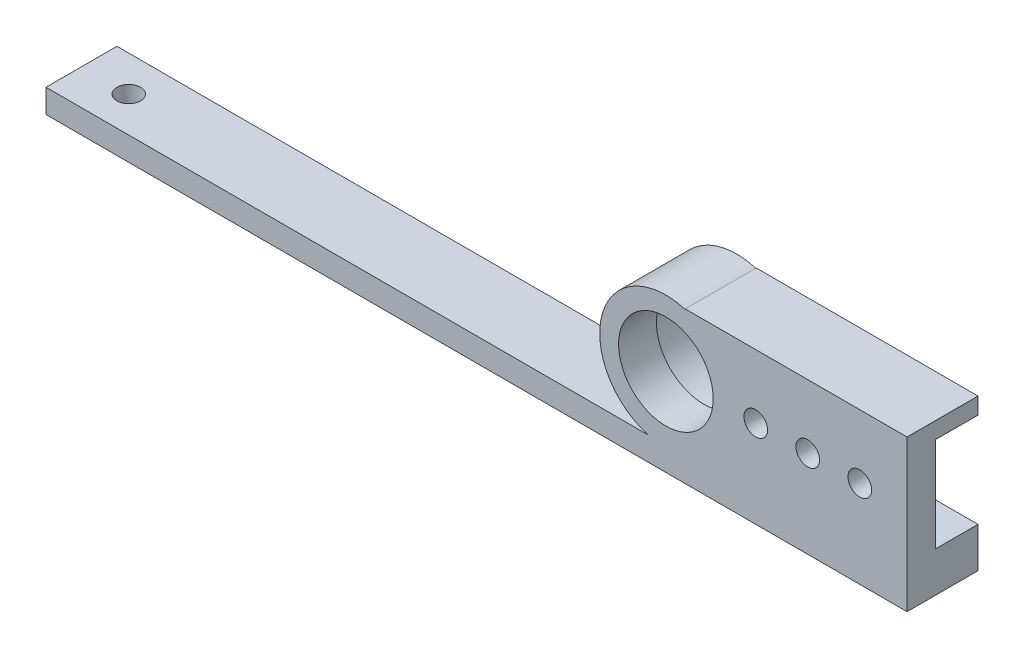
SolidWorks part; units mm, degrees
ref_plane "前视基准面" through (0, 0, 0) normal (0, 0, 1) x (1, 0, 0)
ref_plane "上视基准面" through (0, 0, 0) normal (0, 1, 0) x (1, 0, 0)
ref_plane "右视基准面" through (0, 0, 0) normal (1, 0, 0) x (0, 0, -1)
sketch "草图1" plane through (0, 0, 0) normal (0, 0, 1) x (1, 0, 0)
  line L1 (20, -10) -> (-20, -10)
  line L2 (20, -10) -> (20, 10)
  line L3 (20, 10) -> (-20, 10)
  line L4 (-20, -10) -> (-20, 10)
  line L5 (20, -10) -> (-20, 10) construction
  line L6 (20, 10) -> (-20, -10) construction
  point P0 (0, 0)
  dimension "D1" = 40
  dimension "D2" = 20
extrude "凸台-拉伸1" add sketch "草图1" along normal blind 6
sketch "草图2" plane through (0, 0, 6) normal (0, 0, 1) x (1, 0, 0)
  line L0 (20, -10) -> (20, 10) construction
  circle A0 centre (10, 0) radius 2.5
  circle A1 centre (-1, 0) radius 2.5
  circle A2 centre (-12, 0) radius 2.5
  dimension "D1" = 10
  dimension "D2" = 5
  dimension "D3" = 3
extrude "切除-拉伸1" cut sketch "草图2" against normal through all
sketch "草图3" plane through (0, 0, 6) normal (0, 0, 1) x (1, 0, 0)
  line L0 (20, 13.5) -> (20, 10)
  line L1 (20, -13.5) -> (-26.894, -13.5)
  line L3 (20, 13.5) -> (-26.894, 13.5)
  line L4 (-20, 10) -> (-20, -10)
  line L5 (-20, -10) -> (20, -10)
  line L6 (20, -10) -> (20, 10)
  line L7 (20, 10) -> (-20, 10)
  line L8 (-20, 10) -> (-20, -10)
  line L9 (-20, -10) -> (20, -10)
  line L10 (20, -10) -> (20, 10)
  line L11 (20, 10) -> (-20, 10)
  line L12 (-26.894, -13.5) -> (-26.894, 13.5)
  line L13 (20, -10.0394) -> (-26.894, 13.5) construction
  line L14 (20, 10.0394) -> (-26.894, -13.5) construction
  line L15 (20, -10) -> (20, -13.5)
  circle A0 centre (-31, 0) radius 11
  circle A1 centre (-31, 0) radius 14
  point P2 (0, 0)
  line M10 (-20, 10) -> (-20, -10)
  line M11 (-20, -10) -> (20, -10)
  line M13 (20, 10) -> (-20, 10)
  dimension "D3" = 22
  dimension "D4" = 28
  dimension "D2" = 3.5
  dimension "D1" = 0
extrude "凸台-拉伸2" add sketch "草图3" against normal blind 15 contours L3 A1 L1 L12 A0 | A1 L1 L15 M11 M10 | L1 A1 L8 A0 L12 | L8 A1 L3 L12 A0 | L8 A1 | A1 L0 L3 M10 M13 region at (-1.9449, 11.7771, 6) region at (-1.9449, -11.7771, 6) region at (-23.0173, 9.0328, 6) region at (-27.2274, 11.7946, 6) region at (-18.7882, 0, 6) region at (-23.0173, -9.0328, 6)
sketch "草图5" plane through (0, 0, 6) normal (0, 0, 1) x (1, 0, 0)
  circle A0 centre (-31, 0) radius 10
  circle A1 centre (-31, 0) radius 11 construction
  circle A2 centre (-31, 0) radius 11
  dimension "D1" = 20
extrude "凸台-拉伸3" add sketch "草图5" against normal blind 8
sketch "草图6" plane through (0, 0, 6) normal (0, 0, 1) x (1, 0, 0)
  circle A0 centre (-31, 0) radius 8.5
  circle A1 centre (-31, 0) radius 10 construction
  circle A2 centre (-31, 0) radius 10
  dimension "D1" = 17
sketch "草图9" plane through (0, -13.5, 0) normal (0, -1, 0) x (1, 0, 0)
  circle A0 centre (-18.2368, -1.344) radius 5.5352
sketch "草图10" plane through (20, 0, 0) normal (1, 0, 0) x (0, 0, -1)
  line L1 (9, -13.5) -> (-6, -13.5)
  line L2 (9, -13.5) -> (9, -18.5)
  line L3 (9, -18.5) -> (-6, -18.5)
  line L4 (-6, -13.5) -> (-6, -18.5)
  dimension "D1" = 5
extrude "凸台-拉伸4" add sketch "草图10" against normal blind 200
sketch "草图11" plane through (0, 0, 6) normal (0, 0, 1) x (1, 0, 0)
  line L1 (-28.6193, -11.8661) -> (-25.5243, -11.8661)
  line L2 (-28.6193, -11.8661) -> (-28.6193, -14.961)
  line L3 (-28.6193, -14.961) -> (-25.5243, -14.961)
  line L4 (-25.5243, -11.8661) -> (-25.5243, -14.961)
extrude "凸台-拉伸5" add sketch "草图11" against normal through all
sketch "草图13" plane through (0, -18.5, 0) normal (0, -1, 0) x (1, 0, 0)
  line L0 (-162.0913, 6) -> (-162.0913, -9)
  line L1 (-180, 6) -> (20, 6) construction
  line L2 (-162.0913, 124.91) -> (-162.0913, -245.09) construction
  line L3 (-180, -9) -> (20, -9) construction
sketch "草图14" plane through (0, -18.5, 0) normal (0, -1, 0) x (1, 0, 0)
  line L0 (-118.4338, -15.7251) -> (-118.4338, 9.3691)
  line L1 (-118.4338, 126.7017) -> (-118.4338, -243.2983) construction
sketch "草图15" plane through (0, -18.5, 0) normal (0, -1, 0) x (1, 0, 0)
  line L1 (-118.4338, -15.7251) -> (-184.1416, -15.7251)
  line L2 (-118.4338, -15.7251) -> (-118.4338, 11.9644)
  line L3 (-118.4338, 11.9644) -> (-184.1416, 11.9644)
  line L4 (-184.1416, -15.7251) -> (-184.1416, 11.9644)
sketch "草图16" plane through (0, -18.5, 0) normal (0, -1, 0) x (1, 0, 0)
  line L0 (-162.0913, 6.4407) -> (-162.0913, -38.9947)
  line L1 (-162.0913, 124.91) -> (-162.0913, -245.09) construction
sketch "草图17" plane through (0, -18.5, 0) normal (0, -1, 0) x (1, 0, 0)
  line L0 (-162.0913, 7.3332) -> (-162.0913, -35.3686)
  line L1 (-162.0913, 124.91) -> (-162.0913, -245.09) construction
sketch "草图18" plane through (0, -18.5, 0) normal (0, -1, 0) x (1, 0, 0)
  line L1 (-162.0913, -38.9947) -> (-206.846, -38.9947)
  line L2 (-162.0913, -38.9947) -> (-162.0913, 25.1925)
  line L3 (-162.0913, 25.1925) -> (-206.846, 25.1925)
  line L4 (-206.846, -38.9947) -> (-206.846, 25.1925)
extrude "切除-拉伸3" cut sketch "草图18" against normal through all
sketch "草图19" plane through (0, -18.5, 0) normal (0, -1, 0) x (1, 0, 0)
  line L0 (-162.0913, 6) -> (-162.0913, -9) construction
  line L1 (-162.0913, -1.5) -> (-152.0913, -1.5) construction
  circle A0 centre (-152.0913, -1.5) radius 2.5
  dimension "D1" = 5
  dimension "D2" = 10
extrude "切除-拉伸4" cut sketch "草图19" against normal through all
